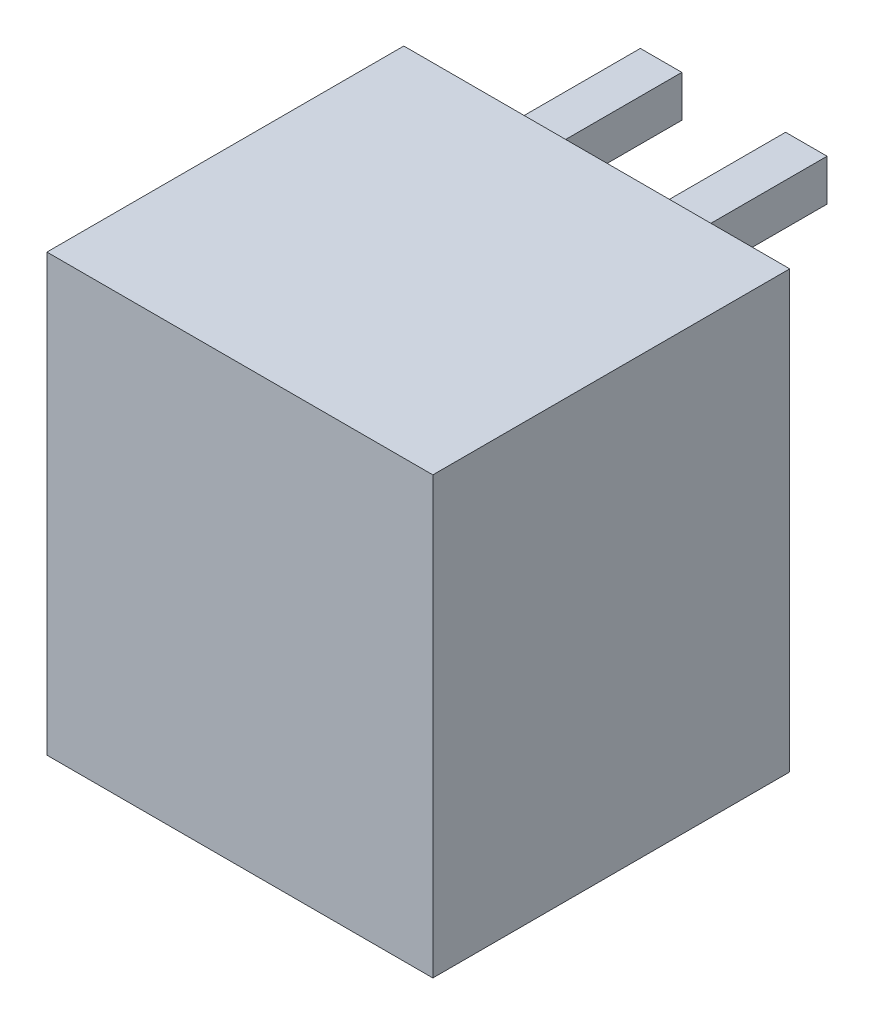
SolidWorks part; units mm, degrees
ref_plane "Спереди" through (0, 0, 0) normal (0, 0, 1) x (1, 0, 0)
ref_plane "Сверху" through (0, 0, 0) normal (0, 1, 0) x (1, 0, 0)
ref_plane "Справа" through (0, 0, 0) normal (1, 0, 0) x (0, 0, -1)
sketch "Эскиз1" plane through (0, 0, 0) normal (0, 0, 1) x (1, 0, 0)
  line L1 (-4.65, -5.25) -> (4.65, -5.25)
  line L2 (-4.65, -5.25) -> (-4.65, 5.25)
  line L3 (-4.65, 5.25) -> (4.65, 5.25)
  line L4 (4.65, -5.25) -> (4.65, 5.25)
  line L5 (-4.65, -5.25) -> (4.65, 5.25) construction
  line L6 (-4.65, 5.25) -> (4.65, -5.25) construction
  point P0 (0, 0)
  dimension "D1" = 9.3
  dimension "D2" = 10.5
extrude "Бобышка-Вытянуть1" add sketch "Эскиз1" along normal blind 8.6
sketch "Эскиз2" plane through (0, -5.25, 0) normal (0, -1, 0) x (1, 0, 0)
  line L0 (-3.65, 6.6) -> (3.65, 6.6)
  line L1 (3.65, 6.6) -> (3.65, 0.2)
  line L2 (3.65, 0.2) -> (1.45, 0.2)
  line L3 (1.45, 0.2) -> (1.45, 1.8)
  line L4 (1.45, 1.8) -> (0.15, 1.8)
  line L5 (0.15, 1.8) -> (0.15, 0.2)
  line L6 (0.15, 0.2) -> (-2.05, 0.2)
  line L7 (-3.65, 6.6) -> (-3.65, 1.8)
  line L8 (-3.65, 1.8) -> (-2.05, 1.8)
  line L9 (-2.05, 1.8) -> (-2.05, 0.2)
  line L10 (4.65, 8.6) -> (4.65, 0) construction
  line L11 (-4.65, 8.6) -> (-4.65, 0) construction
  line L12 (-4.65, 8.6) -> (4.65, 8.6) construction
  dimension "D1" = 4.8
  dimension "D2" = 6.4
  dimension "D3" = 2.2
  dimension "D4" = 2.2
  dimension "D5" = 3.2
  dimension "D6" = 4.8
  dimension "D7" = 1
  dimension "D8" = 2
extrude "Вырез-Вытянуть1" cut sketch "Эскиз2" against normal blind 7
sketch "Эскиз3" plane through (0, 0, 0) normal (0, 0, -1) x (-1, 0, 0)
  line L0 (4.65, -5.25) -> (-4.65, -5.25) construction
  line L1 (2.25, 4.75) -> (1.25, 4.75)
  line L2 (2.25, 4.75) -> (2.25, 3.75)
  line L3 (2.25, 3.75) -> (1.25, 3.75)
  line L4 (1.25, 4.75) -> (1.25, 3.75)
  line L5 (2.25, 4.75) -> (1.25, 3.75) construction
  line L6 (2.25, 3.75) -> (1.25, 4.75) construction
  line L7 (4.65, 5.25) -> (4.65, -5.25) construction
  point P0 (1.75, 4.25)
  dimension "D1" = 1
  dimension "D2" = 9.5
  dimension "D3" = 2.9
extrude "Бобышка-Вытянуть2" add sketch "Эскиз3" along normal blind 3.6 and the other way blind 5
chamfer "Фаска1" distance 0.3 distance2 0.3 4 edges at (-1.25, 4.25, -3.6) (-1.75, 3.75, -3.6) (-2.25, 4.25, -3.6) (-1.75, 4.75, -3.6)
pattern_linear "Линейный массив1" count 2 spacing 3.5 along (1, 0, 0) of "Бобышка-Вытянуть2", "Фаска1"
equation "\"N\"= 2"
equation "\"D1@Эскиз1\"= ( \"N\" - 1 ) * 3.5 + 5.8"
equation "\"D1@Линейный массив1\"=\"N\""
